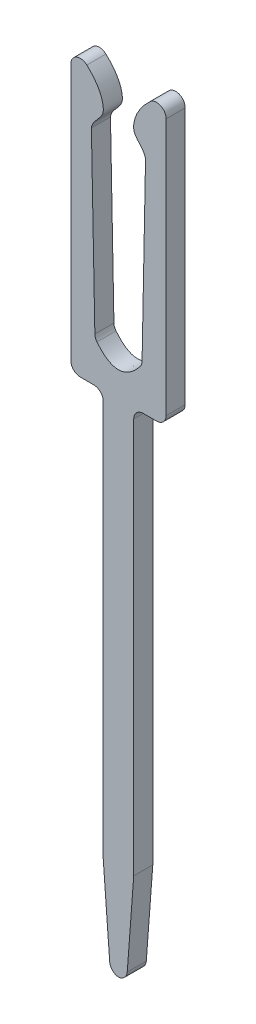
SolidWorks part; units mm, degrees
material "1060 Alloy"
ref_plane "Front Plane" through (0, 0, 0) normal (0, 0, 1) x (1, 0, 0)
ref_plane "Top Plane" through (0, 0, 0) normal (0, 1, 0) x (1, 0, 0)
ref_plane "Right Plane" through (0, 0, 0) normal (1, 0, 0) x (0, 0, -1)
sketch "Sketch1" plane through (0, 0, 0) normal (0, 0, 1) x (1, 0, 0)
  line L0 (-0.32, 1.9994) -> (-0.32, 10.2994)
  line L1 (-0.1839, 0.1844) -> (-0.32, 1.9994)
  line L2 (-0.5677, 15.141) -> (-0.4952, 11.4343)
  line L3 (-1, 10.6994) -> (-1, 16.0898)
  line L4 (0.1839, 0.1844) -> (0.32, 1.9994)
  line L5 (0.32, 1.9994) -> (0.32, 10.2994)
  line L6 (0.52, 10.4994) -> (0.8, 10.4994)
  line L7 (1, 10.6994) -> (1, 16.0898)
  line L8 (0.5677, 15.141) -> (0.4952, 11.4343)
  line L9 (-0.52, 10.4994) -> (-0.8, 10.4994)
  line L10 (0, 11.0326) -> (0, 0) construction
  arc A0 (0, 0) -> (-0.1839, 0.1844) centre (0.0156, 0.1994) cw
  arc A1 (-0.4952, 11.4343) -> (-0.4511, 11.3128) centre (-0.2953, 11.4382) ccw
  arc A2 (-1, 16.0898) -> (-0.663, 16.2356) centre (-0.8, 16.0898) cw
  arc A3 (-0.8, 10.4994) -> (-1, 10.6994) centre (-0.8, 10.6994) cw
  arc A4 (0, 0) -> (0.1839, 0.1844) centre (-0.0156, 0.1994) ccw
  arc A5 (0.32, 10.2994) -> (0.52, 10.4994) centre (0.52, 10.2994) cw
  arc A6 (0.8, 10.4994) -> (1, 10.6994) centre (0.8, 10.6994) ccw
  arc A7 (1, 16.0898) -> (0.663, 16.2356) centre (0.8, 16.0898) ccw
  arc A8 (0.4952, 11.4343) -> (0.4511, 11.3128) centre (0.2953, 11.4382) cw
  arc A9 (-0.32, 10.2994) -> (-0.52, 10.4994) centre (-0.52, 10.2994) ccw
  spline S0 degree 3 poles (0.663, 16.2356) (0.4876, 16.0707) (0.3262, 15.8488) (0.3107, 15.4209) (0.5485, 15.3086) (0.5677, 15.141) knots 0.253308 0.253308 0.253308 0.253308 0.663172 0.707067 1 1 1 1
  spline S1 degree 2 poles (-0.4511, 11.3128) (0, 10.7524) (0.4511, 11.3128) knots 0.043405 0.043405 0.043405 0.956595 0.956595 0.956595
  spline S2 degree 3 poles (-0.663, 16.2356) (-0.4876, 16.0707) (-0.3262, 15.8488) (-0.3107, 15.4209) (-0.5485, 15.3086) (-0.5677, 15.141) knots 0.253308 0.253308 0.253308 0.253308 0.663172 0.707067 1 1 1 1
  dimension "D2" = 0.2
  dimension "D7" = 0.2
  dimension "D8" = 0.68
  dimension "D10" = 0.2
  dimension "D13" = 0.2
  dimension "D1" = 11.0326
  dimension "D3" = 0.1839
  dimension "D4" = 1.815
  dimension "D6" = 8.3
  dimension "D9" = 5.3904
  dimension "D11" = 0.8134
  dimension "D12" = 0.1215
  dimension "D14" = 0.4323
  dimension "D15" = 0.337
  dimension "D16" = 0.9489
  dimension "D17" = 0.5048
extrude "Boss-Extrude1" add sketch "Sketch1" against normal mid plane 0.4
ref_axis "Axis1" through (0, 11.0326, 0) along (0, -1, 0)
